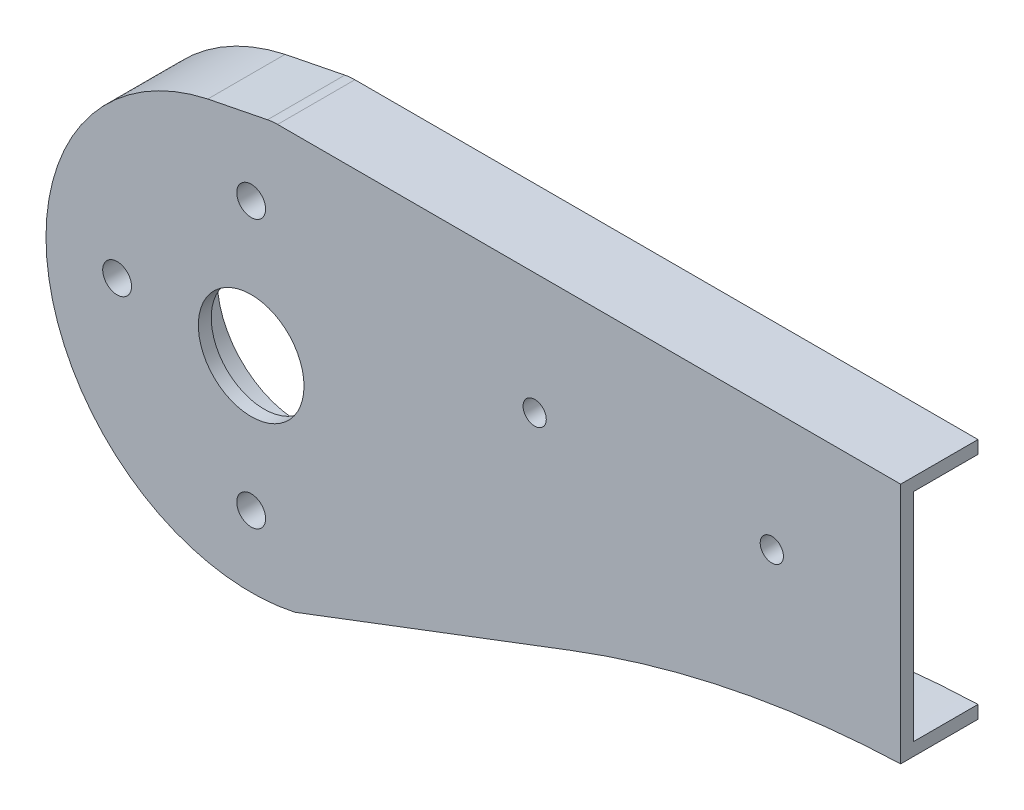
SolidWorks part; units mm, degrees
note: The reader was unsure of these and kept them because the rebuilt part matched: shared geometry of "Schizzo1<3>", "Schizzo3<3>", "Schizzo3<4>", "Schizzo3<5>".
material "ABS generico"
ref_plane "Piano frontale" through (0, 0, 0) normal (0, 0, 1) x (1, 0, 0)
ref_plane "Piano superiore" through (0, 0, 0) normal (0, 1, 0) x (1, 0, 0)
ref_plane "Piano destro" through (0, 0, 0) normal (1, 0, 0) x (0, 0, -1)
sketch "Schizzo1" plane through (0, 0, 0) normal (0, 0, 1) x (1, 0, 0)
  line L0 (5.1235, 41.4) -> (126, 41.4)
  line L1 (126, 41.4) -> (126, -5.6)
  line L2 (126, -5.6) -> (96, -5.6) construction
  line L3 (55, 17.9) -> (101, 17.9) construction
  line L4 (3.1704, 41.2074) -> (-8.4161, 38.9)
  line L5 (-8.4161, 38.9) -> (8.4161, -38.9) construction
  line L6 (8.4161, -38.9) -> (96, -5.6) construction
  line L7 (133.0662, -205.4751) -> (61.1004, -16.1945) construction
  line L8 (8.4161, -38.9) -> (61.9889, -18.5312)
  line L9 (7.8874, -36.4565) -> (61.1004, -16.1945)
  line L10 (-7.8874, 36.4565) -> (3.4151, 38.7074)
  line L11 (5.3683, 38.9) -> (126, 38.9)
  arc A0 (-7.1287, 39.1564) -> (8.4161, -38.9) centre (0, 0) ccw
  circle A1 centre (55, 17.9) radius 7.6836 construction
  circle A2 centre (101, 17.9) radius 7.6836 construction
  arc A3 (126, -5.6) -> (61.9889, -18.5312) centre (133.0662, -205.4751) ccw
  arc A4 (126, -3.0985) -> (61.1004, -16.1945) centre (133.0662, -205.4751) ccw
  arc A5 (-7.8874, 36.4565) -> (7.8874, -36.4565) centre (0, 0) ccw
  arc A6 (5.3683, 38.9) -> (3.4151, 38.7074) centre (5.3683, 28.9) ccw
  arc A7 (5.1235, 41.4) -> (3.1704, 41.2074) centre (5.1235, 31.4) ccw
  point P26 (4.1374, 41.4)
  dimension "D1" = 79.6
  dimension "D11" = 400
  dimension "D12" = 2.5
  dimension "D13" = 2.5
  dimension "D15" = 10
  dimension "D2" = 55
  dimension "D3" = 17.9
  dimension "D4" = 23.5
  dimension "D5" = 30
  dimension "D6" = 47
  dimension "D7" = 25
  dimension "D8" = 12.8
  dimension "D9" = 2.5
  dimension "D10" = 46
  dimension "D14" = 2.5
extrude "Estrusione-Estrusione1" add sketch "Schizzo1" against normal blind 2.5 contours L11 A6 L10 A5 L9 A4 L1 | L0 A7 L4 A0 L8 A3 L1 A4 L9 A5 L10 A6 L11
extrude "Estrusione-Estrusione2" add sketch "Schizzo1<3>" against normal blind 15 contours L0 A7 L4 A0 L8 A3 L1 A4 L9 A5 L10 A6 L11
sketch "Schizzo1<3>" plane through (0, 0, 0) normal (0, 0, 1) x (1, 0, 0) same geometry as "Schizzo1"
sketch "Schizzo2" plane through (0, 0, 0) normal (0, 0, 1) x (1, 0, 0)
  circle A0 centre (0, 0) radius 10.25
  circle A1 centre (0, 0) radius 26 construction
  circle A2 centre (0, -26) radius 2.8
  circle A3 centre (26, 0) radius 2.8 construction
  circle A4 centre (0, 26) radius 2.8
  circle A5 centre (-26, 0) radius 2.8
  dimension "D1" = 20.5
  dimension "D2" = 52
  dimension "D3" = 5.6
extrude "Taglio-Estrusione1" cut sketch "Schizzo2" against normal blind 15
sketch "Schizzo3" plane through (0, 0, -2.5) normal (0, 0, -1) x (-1, 0, 0)
  line L0 (-101, 17.9) -> (-55, 17.9) construction
  line L1 (-126, 38.9) -> (-126, -3.0985) construction
  line L2 (-26, 0) -> (0, 0) construction
  circle A0 centre (0, 0) radius 14.5
  circle A1 centre (0, 0) radius 16.1
  circle A2 centre (0, 0) radius 18.6
  circle A3 centre (0, 26) radius 2.8
  circle A4 centre (26, 0) radius 2.8
  circle A5 centre (0, -26) radius 2.8
  circle A6 centre (-26, 0) radius 2.8
  circle A7 centre (-26, 0) radius 5
  circle A8 centre (0, -26) radius 5
  circle A9 centre (26, 0) radius 5
  circle A10 centre (0, 26) radius 5
  circle A11 centre (-101, 17.9) radius 6.3
  circle A12 centre (-55, 17.9) radius 6.3
  circle A13 centre (-101, 17.9) radius 2.25
  circle A14 centre (-55, 17.9) radius 2.25
  dimension "D1" = 29
  dimension "D2" = 32.2
  dimension "D3" = 37.2
  dimension "D4" = 5.6
  dimension "D5" = 10
  dimension "D9" = 12.6
  dimension "D10" = 4.5
  dimension "D6" = 17.9
  dimension "D7" = 25
  dimension "D8" = 55
  dimension "D11" = 26
extrude "Estrusione-Estrusione3" add sketch "Schizzo3" along normal blind 0.5 contours A1 A0
extrude "Estrusione-Estrusione4" add sketch "Schizzo3<3>" along normal blind 3
sketch "Schizzo3<3>" plane through (0, 0, -2.5) normal (0, 0, -1) x (-1, 0, 0) same geometry as "Schizzo3"
extrude "Estrusione-Estrusione5" add sketch "Schizzo3<4>" along normal blind 5.6
sketch "Schizzo3<4>" plane through (0, 0, -2.5) normal (0, 0, -1) x (-1, 0, 0) same geometry as "Schizzo3"
extrude "Estrusione-Estrusione6" add sketch "Schizzo3<5>" along normal blind 7 contours A2 A1
sketch "Schizzo3<5>" plane through (0, 0, -2.5) normal (0, 0, -1) x (-1, 0, 0) same geometry as "Schizzo3"
chamfer "Smusso1" distance 1.5 angle 45 7 edges at (94.7, 17.9, -5.5) (48.7, 17.9, -5.5) (-21, 0, -2.5) (5, 26, -2.5) (5, -26, -2.5) (31, 0, -2.5) (18.6, 0, -2.5)
sketch "Schizzo4" plane through (0, 0, 0) normal (0, 0, 1) x (1, 0, 0)
  line L0 (55, 17.9) -> (101, 17.9) construction
  line L2 (126, 41.4) -> (126, -5.6) construction
  point P0 (55, 17.9)
  point P2 (101, 17.9)
  dimension "D1" = 25
  dimension "D2" = 55
  dimension "D3" = 17.9
hole_wizard "Foro per Vite M4-1" positions "Schizzo4" profile "Schizzo5" hole size "M4" standard "ISO"
sketch "Schizzo5" plane through (55, 17.9, 0) normal (1, 0, 0) x (0, -1, 0)
  line L0 (0, 0) -> (0, 51.3519)
  line L1 (0, 51.3519) -> (2.25, 50)
  line L2 (2.25, 50) -> (2.25, 0)
  line L5 (2.25, 0) -> (0, 0)
  line L10 (0, 51.3519) -> (-2.25, 50) construction
  line L11 (0, -6.35) -> (0, 107.95) construction
  dimension "Hole Dia." = 4.5
  dimension "Hole Depth" = 50
  dimension "Drill Angle" = 118
